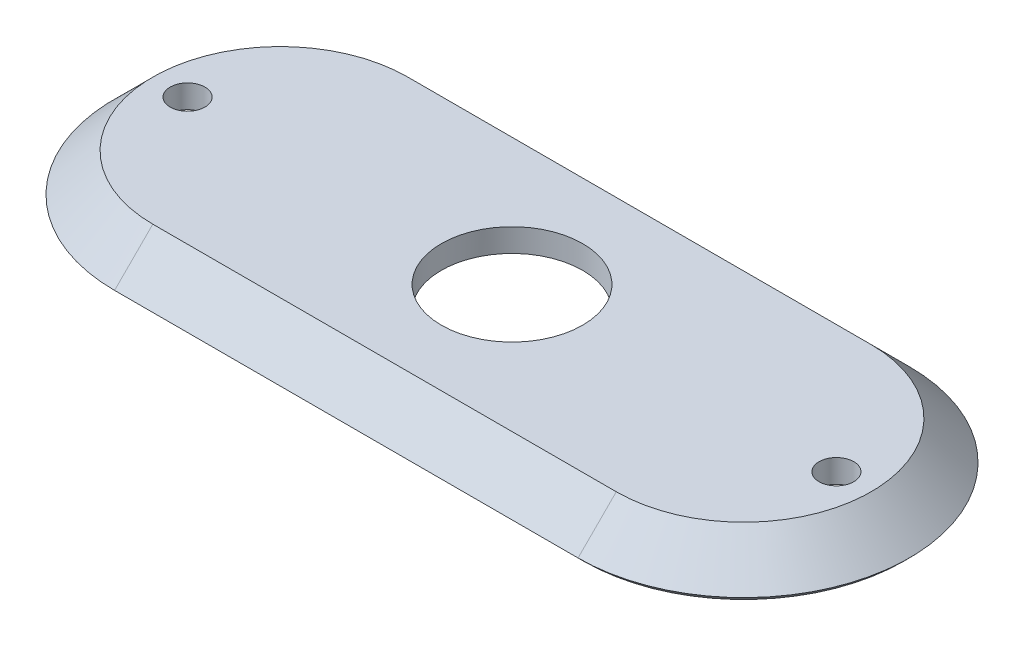
SolidWorks part; units mm, degrees
ref_plane "Plan de face" through (0, 0, 0) normal (0, 0, 1) x (1, 0, 0)
ref_plane "Plan de dessus" through (0, 0, 0) normal (0, 1, 0) x (1, 0, 0)
ref_plane "Plan de droite" through (0, 0, 0) normal (1, 0, 0) x (0, 0, -1)
sketch "Esquisse1" plane through (0, 0, 0) normal (0, 1, 0) x (1, 0, 0)
  line L0 (-20, 0) -> (20, 0) construction
  line L1 (-20, 14.8) -> (20, 14.8)
  line L2 (-20, -14.8) -> (20, -14.8)
  arc A0 (-20, 14.8) -> (-20, -14.8) centre (-20, 0) ccw
  arc A1 (20, -14.8) -> (20, 14.8) centre (20, 0) ccw
  point P3 (0, 0)
  dimension "D1" = 14.8
  dimension "D2" = 40
extrude "Boss.-Extru.1" add sketch "Esquisse1" along normal blind 3.8 draft 45
shell "Coque2" thickness 2 removed face at (0, 0, 0)
chamfer "Chanfrein1" distance 1 angle 45 4 edges at (-34.8, 0, 0) (0, 0, 14.8) (0, 0, -14.8) (34.8, 0, 0) first distance on face at (0, 0, 0)
sketch "Esquisse2" plane through (0, 3.8, 0) normal (0, 1, 0) x (1, 0, 0)
  line L0 (0, 11) -> (0, -11) construction
  line L1 (20, 11) -> (-20, 11) construction
  line L2 (-20, -11) -> (20, -11) construction
  circle A0 centre (-28, 0) radius 1.5
  circle A1 centre (28, 0) radius 1.5
  point P2 (0, 0)
  dimension "D1" = 3
  dimension "D2" = 8
extrude "Enlèv. mat.-Extru.1" cut sketch "Esquisse2" against normal up to next
sketch "Esquisse3" plane through (0, 1.8, 0) normal (0, -1, 0) x (1, 0, 0)
  circle A0 centre (0, 0) radius 6.1
  dimension "D1" = 12.2
extrude "Enlèv. mat.-Extru.2" cut sketch "Esquisse3" against normal up to next
